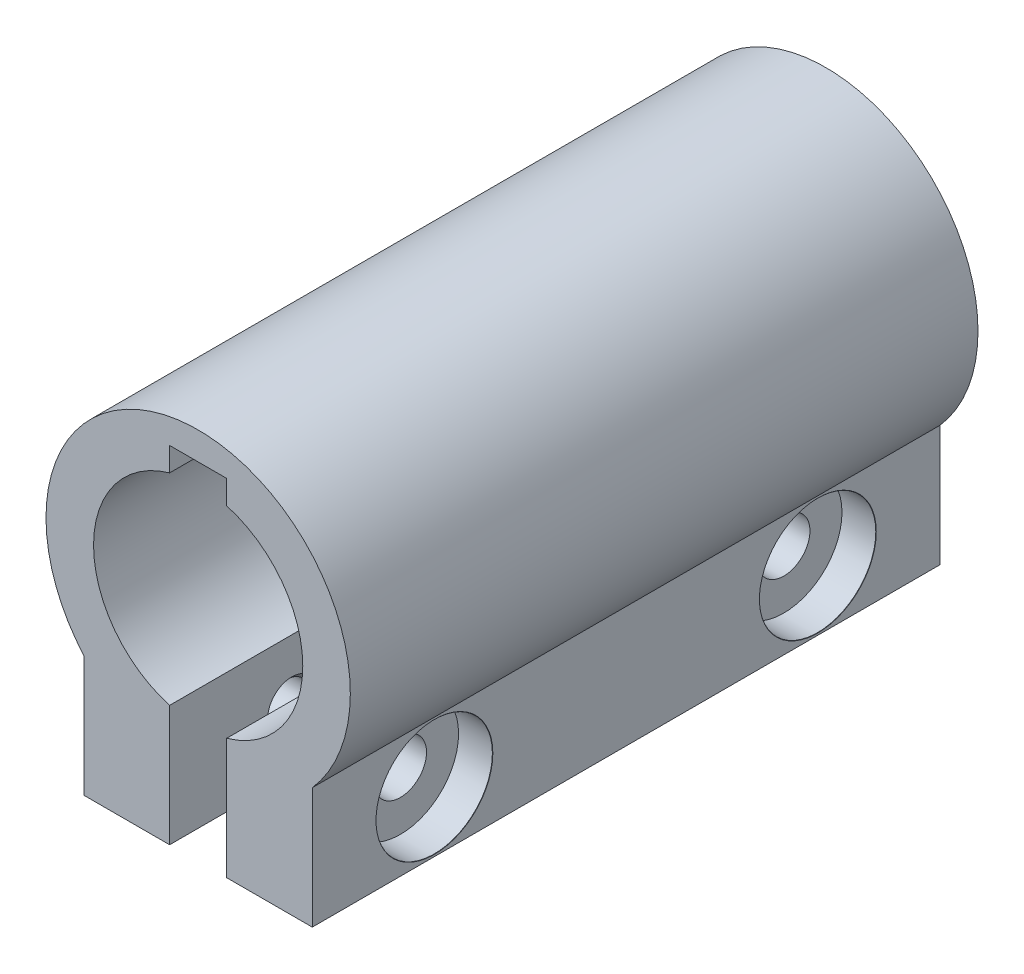
SolidWorks part; units mm, degrees
ref_plane "Front Plane" through (0, 0, 0) normal (0, 0, 1) x (1, 0, 0)
ref_plane "Top Plane" through (0, 0, 0) normal (0, 1, 0) x (1, 0, 0)
ref_plane "Right Plane" through (0, 0, 0) normal (1, 0, 0) x (0, 0, -1)
sketch "Sketch1" plane through (0, 0, 0) normal (0, 0, 1) x (1, 0, 0)
  circle A0 centre (0, 0) radius 11
  circle A1 centre (0, 0) radius 16
  dimension "D1" = 22
  dimension "D2" = 5
extrude "Boss-Extrude1" add sketch "Sketch1" along normal blind 33 and the other way blind 33
sketch "Sketch2" plane through (0, 0, 33) normal (0, 0, 1) x (1, 0, 0)
  line L0 (-3, 10.583) -> (-3, 13.083)
  line L2 (3, 13.083) -> (3, 10.583)
  line L3 (0, 0) -> (0, 13.083) construction
  line L4 (-3, 13.083) -> (0, 13.083)
  line L5 (0, 13.083) -> (3, 13.083)
  line L6 (-3, 10.583) -> (3, 10.583)
  circle A3 centre (0, 0) radius 11 construction
  dimension "D1" = 3
  dimension "D2" = 3
  dimension "D3" = 2.5
  dimension "D4" = 2.5
extrude "Cut-Extrude1" cut sketch "Sketch2" against normal blind 33
mirror "Mirror2" about plane through (0, 0, 0) normal (0, 0, -1) of "Cut-Extrude1"
sketch "Sketch3" plane through (0, 0, 33) normal (0, 0, 1) x (1, 0, 0)
  line L0 (-3, -10.583) -> (-3, -15.7162)
  line L1 (-3, -15.7162) -> (-3, -10.583)
  line L2 (3, -10.583) -> (3, -15.7162)
  line L3 (-3, -10.583) -> (3, -10.583)
  line L4 (-3, -15.7162) -> (-3, -23.283)
  line L5 (-3, -23.283) -> (-12, -23.283)
  line L6 (-12, -23.283) -> (-12, -10.583)
  line L7 (-12, -10.583) -> (-3, -10.583)
  line L8 (3, -15.7162) -> (3, -23.283)
  line L9 (3, -23.283) -> (12, -23.283)
  line L10 (12, -23.283) -> (12, -10.583)
  line L11 (12, -10.583) -> (3, -10.583)
  arc A0 (-3, 10.583) -> (3, 10.583) centre (0, 0) ccw construction
  circle A1 centre (0, 0) radius 16 construction
  circle M6 centre (0, 0) radius 16
  dimension "D1" = 12.7
extrude "Boss-Extrude2" add sketch "Sketch3" against normal through all contours L6 L5 L4 M6 | L9 L10 L8 M6 region at (-7.8946, -18.4352, 33) region at (7.8946, -18.4352, 33)
sketch "Sketch4" plane through (0, 0, 33) normal (0, 0, 1) x (1, 0, 0)
  line L0 (-3, -10.583) -> (-3, -16.2715)
  line L1 (-3, -10.583) -> (3, -10.583)
  line L2 (3, -10.583) -> (3, -15.7162)
  line L3 (-3, -15.7162) -> (-3, -23.283) construction
  line L4 (-3, -16.2715) -> (3, -16.2715)
  line L5 (3, -15.7162) -> (3, -23.283) construction
  line L6 (3, -16.2715) -> (3, -15.7162)
  arc A0 (-3, 10.583) -> (3, 10.583) centre (0, 0) ccw construction
extrude "Cut-Extrude4" cut sketch "Sketch4" against normal through all
sketch "Sketch8" plane through (12, 0, 0) normal (1, 0, 0) x (0, 0, -1)
  line L0 (-33, -16.933) -> (-20.1582, -16.933)
  line L1 (-33, -23.283) -> (-33, -10.583) construction
hole_wizard "CBORE for M5 Hex Head Bolt3" positions "Sketch9" profile "Sketch10" counterbore size "M5" standard "ANSI Metric"
sketch "Sketch9" plane through (12, 0, 0) normal (1, 0, 0) x (0, 0, -1)
  point P0 (-20.1582, -16.933)
sketch "Sketch10" plane through (12, -16.933, 20.1582) normal (0, 1, 0) x (0, 0, -1)
  line L0 (0, 0) -> (0, 11.6524)
  line L1 (0, 11.6524) -> (2.75, 10)
  line L2 (2.75, 10) -> (2.75, 3.58)
  line L3 (2.75, 3.58) -> (6.12, 3.58)
  line L5 (6.12, 3.58) -> (6.12, 0.025)
  line L6 (6.12, 0.025) -> (6.145, 0)
  line L7 (6.145, 0) -> (0, 0)
  line L8 (-6.12, 0.025) -> (-6.145, 0) construction
  line L10 (0, 11.6524) -> (-2.75, 10) construction
  line L11 (0, -6.35) -> (0, 107.95) construction
  dimension "Hole Dia." = 5.5
  dimension "Hole Depth" = 10
  dimension "C'Bore Dia." = 12.24
  dimension "C'Bore Depth" = 3.58
  dimension "Near C'Sink Dia." = 12.29
  dimension "Near C'Sink Angle" = 90
  dimension "Drill Angle" = 118
mirror "Mirror3" about plane through (0, 0, 0) normal (0, 0, 1) of "CBORE for M5 Hex Head Bolt3"
sketch "Sketch12" plane through (-3, 0, 0) normal (1, 0, 0) x (0, 0, -1)
  circle A0 centre (-20.1582, -16.933) radius 3.2234
  circle A1 centre (-20.1582, -16.933) radius 2.75 construction
hole_wizard "M5x0.8 Tapped Hole1" positions "Sketch13" profile "Sketch14" tap size "M5x0.8" standard "ANSI Metric"
sketch "Sketch13" plane through (-3, 0, 0) normal (1, 0, 0) x (0, 0, -1)
  point P0 (-20.1582, -16.933)
sketch "Sketch14" plane through (-3, -16.933, 20.1582) normal (0, 1, 0) x (0, 0, -1)
  line L0 (0, 0) -> (0, 13.6618)
  line L1 (0, 13.6618) -> (2.1, 12.4)
  line L2 (2.1, 12.4) -> (2.1, 0.425)
  line L3 (2.1, 0.425) -> (2.525, 0)
  line L5 (2.525, 0) -> (0, 0)
  line L6 (-2.1, 0.425) -> (-2.525, 0) construction
  line L10 (0, 13.6618) -> (-2.1, 12.4) construction
  line L11 (0, -6.35) -> (0, 107.95) construction
  dimension "Tap Drill Dia." = 4.2
  dimension "Tap Drill Depth" = 12.4
  dimension "Near C'Sink Dia." = 5.05
  dimension "Near C'Sink Angle" = 90
  dimension "Drill Angle" = 118
cosmetic thread "Hole Thread1" parameters "D1"=9, "D2"=5
mirror "Mirror4" about plane through (0, 0, 0) normal (0, 0, 1) of "M5x0.8 Tapped Hole1"
